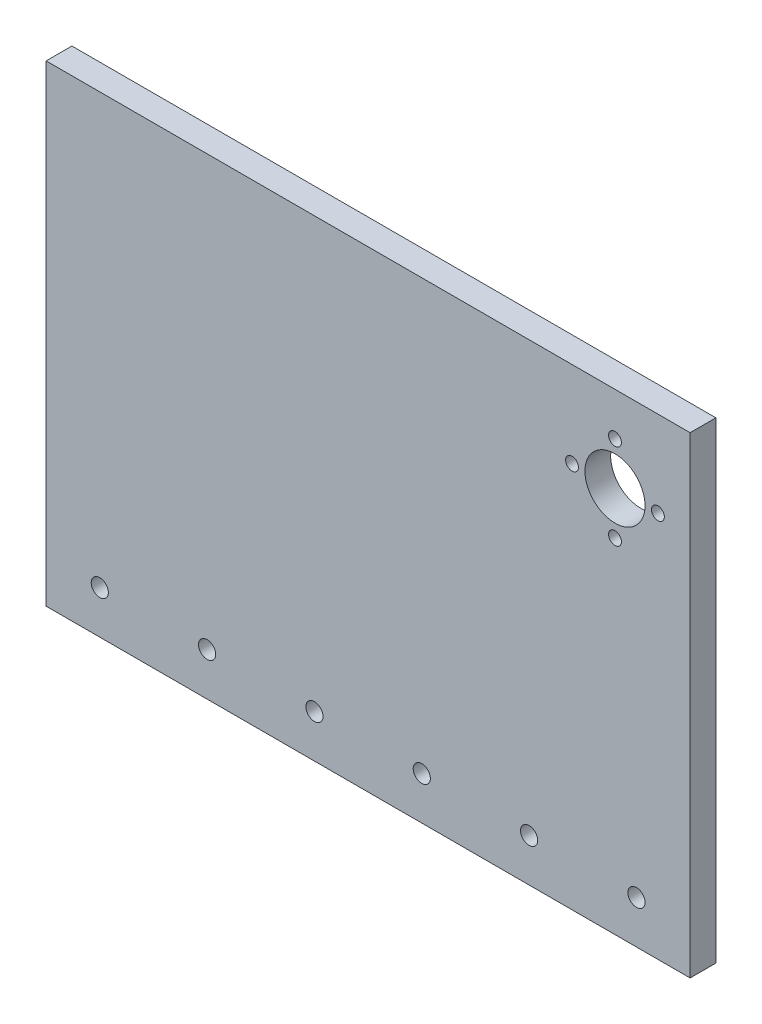
SolidWorks part; units mm, degrees
ref_plane "Plan de face" through (0, 0, 0) normal (0, 0, 1) x (1, 0, 0)
ref_plane "Plan de dessus" through (0, 0, 0) normal (0, 1, 0) x (1, 0, 0)
ref_plane "Plan de droite" through (0, 0, 0) normal (1, 0, 0) x (0, 0, -1)
sketch "Esquisse1" plane through (0, 0, 0) normal (0, 0, 1) x (1, 0, 0)
  line L1 (0, 0) -> (150, 0)
  line L2 (0, 0) -> (0, 110)
  line L3 (0, 110) -> (150, 110)
  line L4 (150, 0) -> (150, 110)
  dimension "D1" = 110
  dimension "D2" = 150
extrude "Boss.-Extru.1" add sketch "Esquisse1" along normal blind 6
sketch "Esquisse2" plane through (0, 0, 6) normal (0, 0, 1) x (1, 0, 0)
  line L0 (87.5, 0) -> (87.5, 108.7105) construction
  line L1 (0, 0) -> (150, 0) construction
  line L2 (0, 110) -> (0, 0) construction
  line L3 (137.5, 10) -> (112.5, 10) construction
  line L4 (112.5, 10) -> (87.5, 10) construction
  line L5 (37.5, 10) -> (62.5, 10) construction
  line L6 (12.5, 10) -> (37.5, 10) construction
  circle A0 centre (112.5, 10) radius 2
  circle A1 centre (137.5, 10) radius 2
  circle A2 centre (37.5, 10) radius 2
  circle A3 centre (62.5, 10) radius 2
  circle A4 centre (87.5, 10) radius 2
  circle A5 centre (12.5, 10) radius 2
  dimension "D2" = 4
  dimension "D3" = 25
  dimension "D4" = 25
  dimension "D6" = 25
  dimension "D1" = 10
  dimension "D5" = 87.5
extrude "Enlèv. mat.-Extru.1" cut sketch "Esquisse2" against normal through all
sketch "Esquisse3" plane through (0, 0, 6) normal (0, 0, 1) x (1, 0, 0)
  line L0 (0, 0) -> (150, 0) construction
  circle A0 centre (132.5, 90) radius 7
  circle A1 centre (87.5, 10) radius 2 construction
  dimension "D1" = 14
  dimension "D2" = 90
  dimension "D3" = 45
extrude "Enlèv. mat.-Extru.2" cut sketch "Esquisse3" against normal through all
sketch "Esquisse4" plane through (0, 0, 6) normal (0, 0, 1) x (1, 0, 0)
  line L0 (132.5, 90) -> (132.5, 100) construction
  circle A0 centre (132.5, 100) radius 1.5
  circle A1 centre (142.5, 90) radius 1.5
  circle A2 centre (132.5, 80) radius 1.5
  circle A3 centre (122.5, 90) radius 1.5
  point P12 (132.5, 90)
  dimension "D1" = 3
  dimension "D2" = 10
  dimension "D3" = 4
extrude "Enlèv. mat.-Extru.3" cut sketch "Esquisse4" against normal up to vertex (6 mm away) up to point (150, 110, 0)
